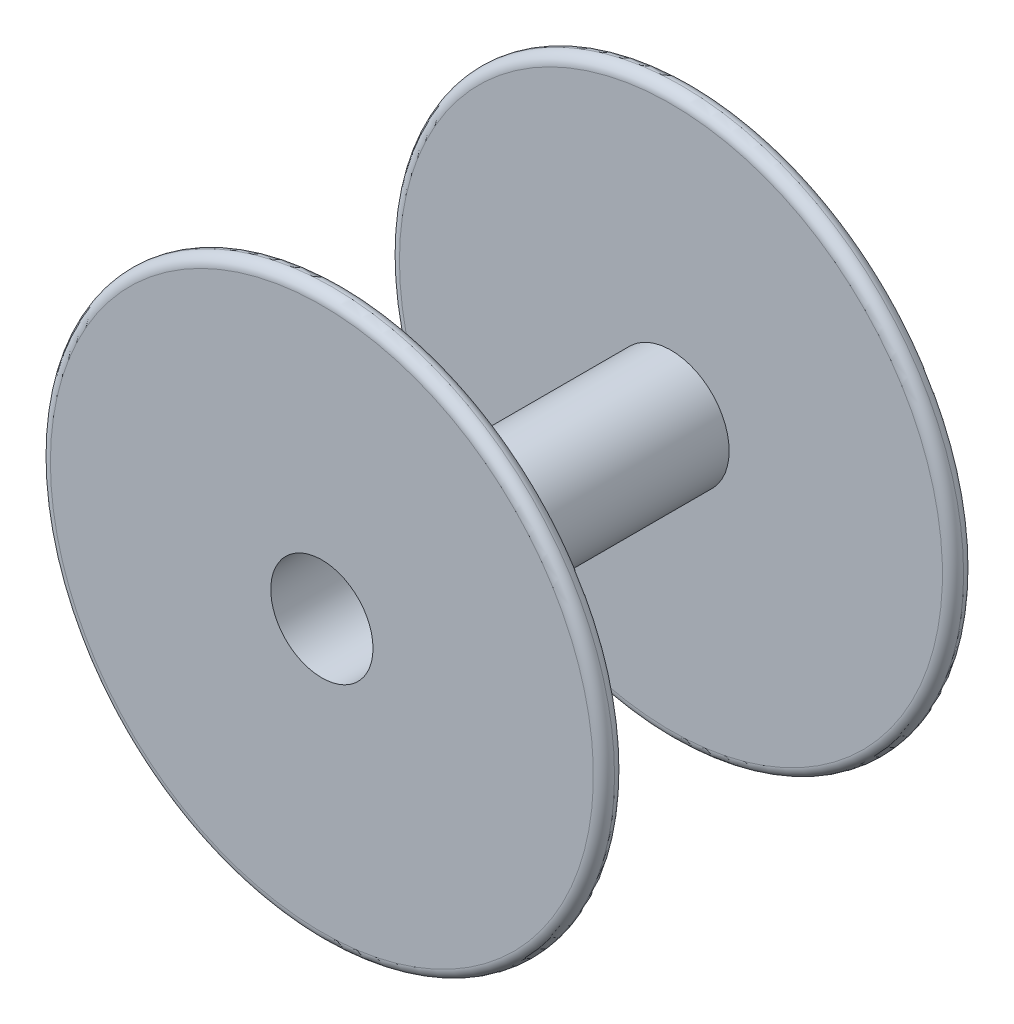
SolidWorks part; units mm, degrees
ref_plane "Front Plane" through (0, 0, 0) normal (0, 0, 1) x (1, 0, 0)
ref_plane "Top Plane" through (0, 0, 0) normal (0, 1, 0) x (1, 0, 0)
ref_plane "Right Plane" through (0, 0, 0) normal (1, 0, 0) x (0, 0, -1)
sketch "Sketch1" plane through (0, 0, 0) normal (1, 0, 0) x (0, 0, -1)
  line L0 (-52.5, 80) -> (-52.5, 14.5)
  line L1 (-52.5, 14.5) -> (52.5, 14.5)
  line L2 (46.5, 80) -> (52.5, 80)
  line L3 (46.5, 16.5) -> (46.5, 80)
  line L4 (52.5, 80) -> (52.5, 14.5)
  line L5 (46.5, 16.5) -> (-46.5, 16.5)
  line L6 (-46.5, 16.5) -> (-46.5, 80)
  line L7 (-46.5, 80) -> (-52.5, 80)
  line L8 (0, 0) -> (44.9554, 0) construction
  line L9 (0, 0) -> (0, 82.244) construction
  point P13 (0, 16.5)
  point P14 (0, 14.5)
  dimension "D1" = 33
  dimension "D2" = 2
  dimension "D3" = 160
  dimension "D4" = 105
  dimension "D5" = 6
revolve "Revolve1" add sketch "Sketch1" angle 360 about L8
fillet "Fillet1" radius 3 4 edges at (80, 0, 52.5) (80, 0, 46.5) (80, 0, -52.5) (80, 0, -46.5)
